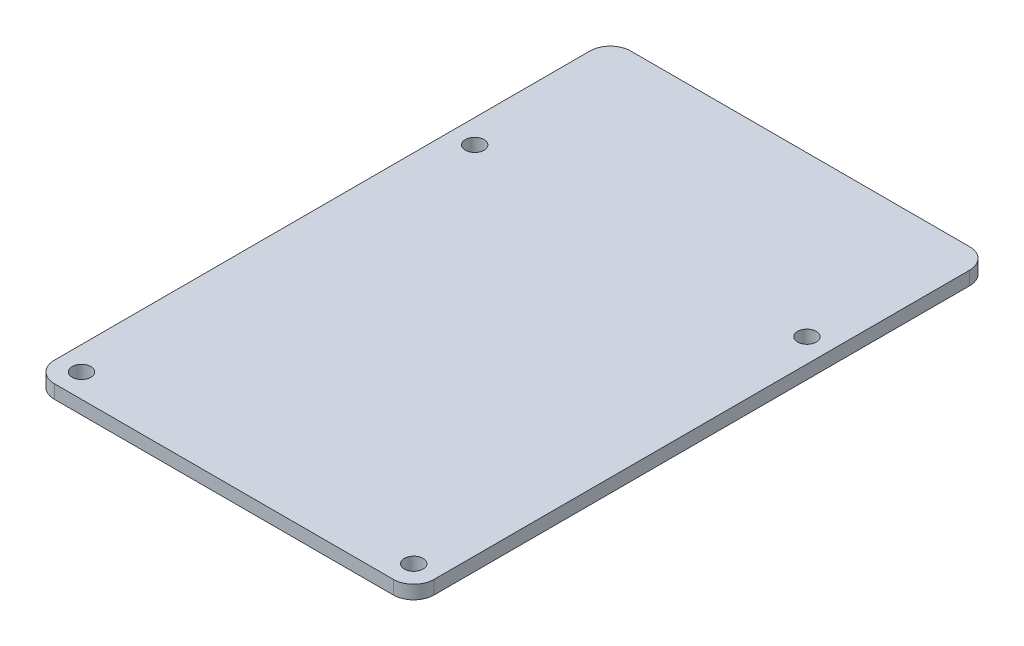
SolidWorks part; units mm, degrees
ref_plane "Front Plane" through (0, 0, 0) normal (0, 0, 1) x (1, 0, 0)
ref_plane "Top Plane" through (0, 0, 0) normal (0, 1, 0) x (1, 0, 0)
ref_plane "Right Plane" through (0, 0, 0) normal (1, 0, 0) x (0, 0, -1)
sketch "Sketch1" plane through (0, 0, 0) normal (0, 1, 0) x (1, 0, 0)
  line L1 (-28, -42.5) -> (28, -42.5)
  line L2 (-28, -42.5) -> (-28, 42.5)
  line L3 (-28, 42.5) -> (28, 42.5)
  line L4 (28, -42.5) -> (28, 42.5)
  line L5 (-28, -42.5) -> (28, 42.5) construction
  line L6 (-28, 42.5) -> (28, -42.5) construction
  circle A0 centre (-24.5, -39) radius 1.375
  circle A1 centre (-24.5, 19) radius 1.375
  circle A2 centre (24.5, 19) radius 1.375
  circle A3 centre (24.5, -39) radius 1.375
  point P0 (0, 0)
  dimension "D6" = 2.75
  dimension "D1" = 56
  dimension "D2" = 85
  dimension "D3" = 3.5
  dimension "D4" = 3.5
  dimension "D5" = 49
  dimension "D7" = 58
  dimension "D8" = 49
extrude "Boss-Extrude1" add sketch "Sketch1" along normal blind 2
fillet "Fillet1" radius 3 4 edges at (-28, 1, -42.5) (28, 1, -42.5) (28, 1, 42.5) (-28, 1, 42.5)
